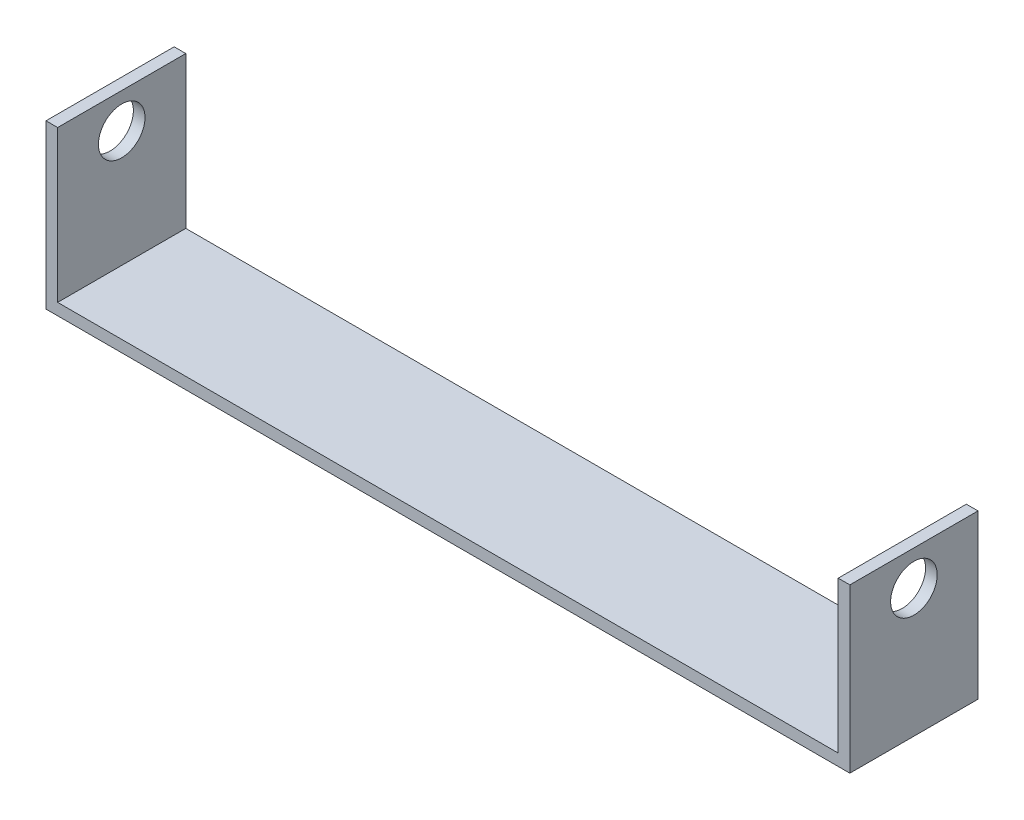
SolidWorks part; units mm, degrees
ref_plane "Front Plane" through (0, 0, 0) normal (0, 0, 1) x (1, 0, 0)
ref_plane "Top Plane" through (0, 0, 0) normal (0, 1, 0) x (1, 0, 0)
ref_plane "Right Plane" through (0, 0, 0) normal (1, 0, 0) x (0, 0, -1)
sketch "Sketch1" plane through (0, 0, 0) normal (0, 0, 1) x (1, 0, 0)
  line L0 (-172.5, 0) -> (172.5, 0)
  line L1 (-172.5, 0) -> (-172.5, 70)
  line L2 (172.5, 0) -> (172.5, 70)
  line L3 (167.5, 5) -> (167.5, 70)
  line L4 (-167.5, 5) -> (167.5, 5)
  line L5 (-167.5, 5) -> (-167.5, 70)
  line L6 (-172.5, 70) -> (-167.5, 70)
  line L7 (167.5, 70) -> (172.5, 70)
  dimension "D1" = 345
  dimension "D2" = 70
  dimension "D3" = 5
extrude "Boss-Extrude1" add sketch "Sketch1" along normal blind 27.5 and the other way blind 27.5
sketch "Sketch2" plane through (172.5, 0, 0) normal (1, 0, 0) x (0, 0, -1)
  line L0 (27.5, 70) -> (-27.5, 70) construction
  circle A0 centre (0, 55) radius 10
  dimension "D1" = 20
  dimension "D2" = 15
extrude "Cut-Extrude1" cut sketch "Sketch2" against normal through all
